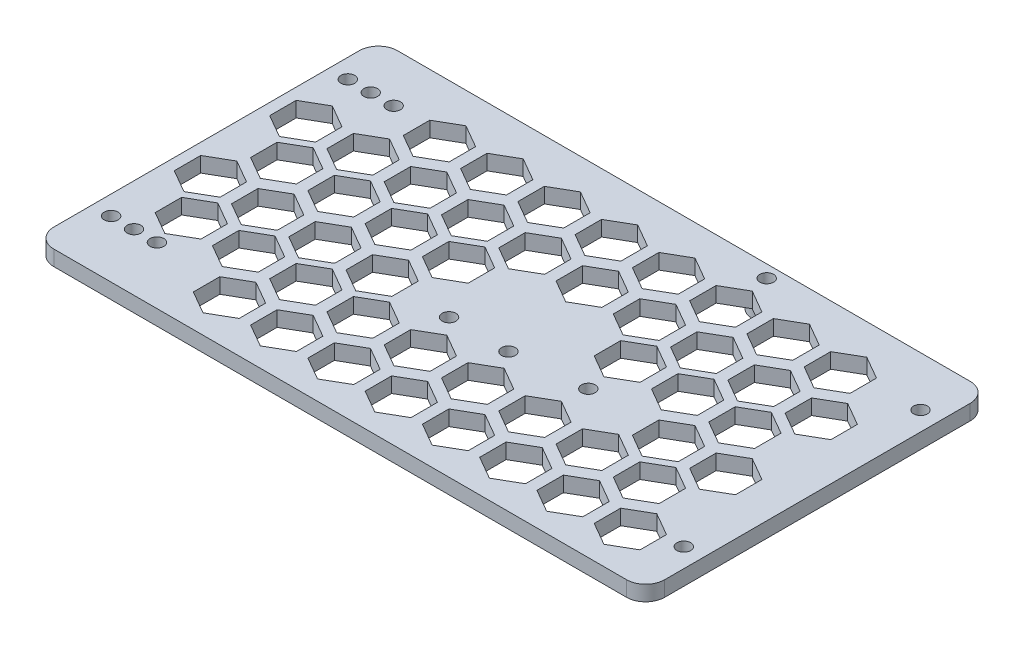
SolidWorks part; units mm, degrees
material "PLA 100% Infill"
ref_plane "Front Plane" through (0, 0, 0) normal (0, 0, 1) x (1, 0, 0)
ref_plane "Top Plane" through (0, 0, 0) normal (0, 1, 0) x (1, 0, 0)
ref_plane "Right Plane" through (0, 0, 0) normal (1, 0, 0) x (0, 0, -1)
sketch "Sketch1" plane through (0, 0, 0) normal (0, 1, 0) x (1, 0, 0)
  line L0 (-160, -45) -> (0, -45) construction
  line L1 (0, 0) -> (-160, 0)
  line L2 (0, 0) -> (0, -90)
  line L3 (0, -90) -> (-160, -90)
  line L4 (-160, 0) -> (-160, -90)
  line L5 (-80, 0) -> (-80, -90) construction
  line L6 (-72.22, -53.71) -> (-87.78, -53.71) construction
  line L7 (-69.22, -51.81) -> (-90.78, -51.81)
  line L8 (-69.22, -56.71) -> (-90.78, -56.71)
  line L9 (-69.22, -56.71) -> (-69.22, -38.71)
  line L10 (-69.22, -38.71) -> (-90.78, -38.71)
  line L11 (-90.78, -56.71) -> (-90.78, -38.71)
  line L12 (-69.22, -56.71) -> (-90.78, -38.71) construction
  line L13 (-69.22, -38.71) -> (-90.78, -56.71) construction
  line L14 (-86.748, -51.81) -> (-84.7188, -53.71)
  line L15 (-73.252, -51.81) -> (-75.2812, -53.71)
  circle A0 centre (-155, -75) radius 1.8
  circle A1 centre (-5, -75) radius 1.8
  circle A2 centre (-5, -13) radius 1.8
  circle A3 centre (-155, -13) radius 1.8
  circle A4 centre (-149, -75) radius 1.8
  circle A5 centre (-149, -13) radius 1.8
  circle A6 centre (-143, -75) radius 1.8
  circle A7 centre (-143, -13) radius 1.8
  circle A8 centre (-72.22, -53.71) radius 1.8
  circle A9 centre (-87.78, -53.71) radius 1.8
  arc A12 (-74.6202, -51.81) -> (-72.8292, -56.71) centre (-72.22, -53.71) ccw
  arc A13 (-85.3798, -51.81) -> (-87.1708, -56.71) centre (-87.78, -53.71) cw
  circle A14 centre (-53.31, -51.7) radius 1.8
  circle A15 centre (-55.02, -3.27) radius 1.8
  point P35 (-80, -58.2721)
  point P45 (-60.3341, -6.5631)
  point P48 (-59.8571, 0)
  point P52 (-57.6313, -4.9732)
  dimension "D3" = 3.6
  dimension "D8" = 62
  dimension "D9" = 5
  dimension "D4" = 30
  dimension "D11" = 3.6
  dimension "D14" = 33.29
  dimension "D20" = 0.1
  dimension "D21" = 3.0612
  dimension "D26" = 3.27
  dimension "D1" = 160
  dimension "D2" = 90
  dimension "D5" = 5
  dimension "D10" = 3
  dimension "D12" = 15.56
  dimension "D13" = 15.56
  dimension "D15" = 3
  dimension "D16" = 3
  dimension "D17" = 3
  dimension "D18" = 18
  dimension "D19" = 3
  dimension "D22" = 4.032
  dimension "D23" = 1.71
  dimension "D24" = 48.43
  dimension "D25" = 55.02
  dimension "D6" = 2
  dimension "D7" = 2
extrude "Boss-Extrude1" add sketch "Sketch1" along normal blind 4 contours L1 L4 L3 L2 A7 A6 A5 A4 A3 A2 A1 A0 L8 L11 L10 L9 | L8 L9 L10 L11 L7 A8 | L7 L8 | L11 L7 L9 L10 | L7 A12 L15 | L15 A12 L8 L9 L7 A8 | A13 L7 L14 | A13 L14 L7 L11 L8 A9 region at (-1.8358, 0, 45) region at (-69.2979, 0, 54.26) region at (-80, 0, 45.26) region at (-74.479, 0, 52.4875) region at (-80, 0, 54.3578) region at (-85.521, 0, 52.4875) region at (-88.9754, 0, 56.6321)
fillet "Fillet1" radius 5 4 edges at (-160, 2, 0) (0, 2, 0) (0, 2, 90) (-160, 2, 90)
extrude "Cut-Extrude1" cut sketch "Sketch1<3>" along normal blind 3 contours L7 A13 L8 A12 | L11 L7 L9 L10 | A13 L7 L14 | L7 A12 L15 region at (-80, 0, 45.26) region at (-74.479, 0, 52.4875) region at (-80, 0, 54.3578) region at (-85.521, 0, 52.4875)
sketch "Sketch1<3>" plane through (0, 0, 0) normal (0, 1, 0) x (1, 0, 0) same geometry as "Sketch1"
sketch "Sketch2" plane through (0, 0, 0) normal (0, -1, 0) x (1, 0, 0)
  line L0 (-5, 0) -> (-155, 0) construction
  line L1 (-52.7163, 0) -> (-57.3237, 0)
  circle A0 centre (-53.31, 51.7) radius 4
  arc A1 (-52.7163, 0) -> (-57.3237, 0) centre (-55.02, 3.27) ccw
  circle A2 centre (-55.02, 3.27) radius 1.8 construction
  circle A3 centre (-53.31, 51.7) radius 1.8 construction
  circle A4 centre (-55.02, 3.27) radius 1.8
  circle A5 centre (-53.31, 51.7) radius 1.8
  dimension "D1" = 8
extrude "Boss-Extrude2" add sketch "Sketch2" along normal blind 3
sketch "Sketch3" plane through (0, 0, 0) normal (0, -1, 0) x (1, 0, 0)
  line L0 (-57.3237, 0) -> (-155, 0) construction
  line L5 (-114.9991, 24.5364) -> (-115.0009, 31.4646)
  line L6 (-123, 11.5359) -> (-123, 18.4641)
  line L7 (-160, 5) -> (-160, 85) construction
  line L164 (-123, 18.4641) -> (-129, 21.9282)
  line L165 (-129, 21.9282) -> (-135, 18.4641)
  line L166 (-135, 18.4641) -> (-135, 11.5359)
  line L167 (-135, 11.5359) -> (-129, 8.0718)
  line L168 (-129, 8.0718) -> (-123, 11.5359)
  line L169 (-115.0009, 31.4646) -> (-121.0009, 34.9287)
  line L170 (-121.0009, 34.9287) -> (-127, 31.463)
  line L171 (-127, 31.463) -> (-127, 24.5348)
  line L172 (-127, 24.5348) -> (-120.9991, 21.0723)
  line L173 (-120.9991, 21.0723) -> (-114.9991, 24.5364)
  line L174 (-108, 11.5359) -> (-108, 18.4641)
  line L175 (-108, 18.4641) -> (-114, 21.9282)
  line L176 (-114, 21.9282) -> (-120, 18.4641)
  line L177 (-120, 18.4641) -> (-120, 11.5359)
  line L178 (-120, 11.5359) -> (-114, 8.0718)
  line L179 (-114, 8.0718) -> (-108, 11.5359)
  line L180 (-99.9991, 24.5364) -> (-100.0009, 31.4646)
  line L181 (-100.0009, 31.4646) -> (-106.0009, 34.9287)
  line L182 (-106.0009, 34.9287) -> (-112, 31.463)
  line L183 (-112, 31.463) -> (-112, 24.5348)
  line L184 (-112, 24.5348) -> (-105.9991, 21.0723)
  line L185 (-105.9991, 21.0723) -> (-99.9991, 24.5364)
  line L186 (-93, 11.5359) -> (-93, 18.4641)
  line L187 (-93, 18.4641) -> (-99, 21.9282)
  line L188 (-99, 21.9282) -> (-105, 18.4641)
  line L189 (-105, 18.4641) -> (-105, 11.5359)
  line L190 (-105, 11.5359) -> (-99, 8.0718)
  line L191 (-99, 8.0718) -> (-93, 11.5359)
  line L192 (-84.9991, 24.5364) -> (-85.0009, 31.4646)
  line L193 (-85.0009, 31.4646) -> (-91.0009, 34.9287)
  line L194 (-91.0009, 34.9287) -> (-97, 31.463)
  line L195 (-97, 31.463) -> (-97, 24.5348)
  line L196 (-97, 24.5348) -> (-90.9991, 21.0723)
  line L197 (-90.9991, 21.0723) -> (-84.9991, 24.5364)
  line L198 (-78, 11.5359) -> (-78, 18.4641)
  line L199 (-78, 18.4641) -> (-84, 21.9282)
  line L200 (-84, 21.9282) -> (-90, 18.4641)
  line L201 (-90, 18.4641) -> (-90, 11.5359)
  line L202 (-90, 11.5359) -> (-84, 8.0718)
  line L203 (-84, 8.0718) -> (-78, 11.5359)
  line L204 (-69.9991, 24.5364) -> (-70.0009, 31.4646)
  line L205 (-70.0009, 31.4646) -> (-76.0009, 34.9287)
  line L206 (-76.0009, 34.9287) -> (-82, 31.463)
  line L207 (-82, 31.463) -> (-82, 24.5348)
  line L208 (-82, 24.5348) -> (-75.9991, 21.0723)
  line L209 (-75.9991, 21.0723) -> (-69.9991, 24.5364)
  line L210 (-63, 11.5359) -> (-63, 18.4641)
  line L211 (-63, 18.4641) -> (-69, 21.9282)
  line L212 (-69, 21.9282) -> (-75, 18.4641)
  line L213 (-75, 18.4641) -> (-75, 11.5359)
  line L214 (-75, 11.5359) -> (-69, 8.0718)
  line L215 (-69, 8.0718) -> (-63, 11.5359)
  line L216 (-54.9991, 24.5364) -> (-55.0009, 31.4646)
  line L217 (-55.0009, 31.4646) -> (-61.0009, 34.9287)
  line L218 (-61.0009, 34.9287) -> (-67, 31.463)
  line L219 (-67, 31.463) -> (-67, 24.5348)
  line L220 (-67, 24.5348) -> (-60.9991, 21.0723)
  line L221 (-60.9991, 21.0723) -> (-54.9991, 24.5364)
  line L222 (-48, 11.5359) -> (-48, 18.4641)
  line L223 (-48, 18.4641) -> (-54, 21.9282)
  line L224 (-54, 21.9282) -> (-60, 18.4641)
  line L225 (-60, 18.4641) -> (-60, 11.5359)
  line L226 (-60, 11.5359) -> (-54, 8.0718)
  line L227 (-54, 8.0718) -> (-48, 11.5359)
  line L228 (-39.9991, 24.5364) -> (-40.0009, 31.4646)
  line L229 (-40.0009, 31.4646) -> (-46.0009, 34.9287)
  line L230 (-46.0009, 34.9287) -> (-52, 31.463)
  line L231 (-52, 31.463) -> (-52, 24.5348)
  line L232 (-52, 24.5348) -> (-45.9991, 21.0723)
  line L233 (-45.9991, 21.0723) -> (-39.9991, 24.5364)
  line L234 (-33, 11.5359) -> (-33, 18.4641)
  line L235 (-33, 18.4641) -> (-39, 21.9282)
  line L236 (-39, 21.9282) -> (-45, 18.4641)
  line L237 (-45, 18.4641) -> (-45, 11.5359)
  line L238 (-45, 11.5359) -> (-39, 8.0718)
  line L239 (-39, 8.0718) -> (-33, 11.5359)
  line L240 (-24.9991, 24.5364) -> (-25.0009, 31.4646)
  line L241 (-25.0009, 31.4646) -> (-31.0009, 34.9287)
  line L242 (-31.0009, 34.9287) -> (-37, 31.463)
  line L243 (-37, 31.463) -> (-37, 24.5348)
  line L244 (-37, 24.5348) -> (-30.9991, 21.0723)
  line L245 (-30.9991, 21.0723) -> (-24.9991, 24.5364)
  line L246 (-18, 11.5359) -> (-18, 18.4641)
  line L247 (-18, 18.4641) -> (-24, 21.9282)
  line L248 (-24, 21.9282) -> (-30, 18.4641)
  line L249 (-30, 18.4641) -> (-30, 11.5359)
  line L250 (-30, 11.5359) -> (-24, 8.0718)
  line L251 (-24, 8.0718) -> (-18, 11.5359)
  line L252 (-9.9991, 24.5364) -> (-10.0009, 31.4646)
  line L253 (-10.0009, 31.4646) -> (-16.0009, 34.9287)
  line L254 (-16.0009, 34.9287) -> (-22, 31.463)
  line L255 (-22, 31.463) -> (-22, 24.5348)
  line L256 (-22, 24.5348) -> (-15.9991, 21.0723)
  line L257 (-15.9991, 21.0723) -> (-9.9991, 24.5364)
  line L258 (-108, 36.5359) -> (-108, 43.4641)
  line L259 (-108, 43.4641) -> (-114, 46.9282)
  line L260 (-114, 46.9282) -> (-120, 43.4641)
  line L261 (-120, 43.4641) -> (-120, 36.5359)
  line L262 (-120, 36.5359) -> (-114, 33.0718)
  line L263 (-114, 33.0718) -> (-108, 36.5359)
  line L264 (-99.9991, 49.5364) -> (-100.0009, 56.4646)
  line L265 (-100.0009, 56.4646) -> (-106.0009, 59.9287)
  line L266 (-106.0009, 59.9287) -> (-112, 56.463)
  line L267 (-112, 56.463) -> (-112, 49.5348)
  line L268 (-112, 49.5348) -> (-105.9991, 46.0723)
  line L269 (-105.9991, 46.0723) -> (-99.9991, 49.5364)
  line L270 (-93, 36.5359) -> (-93, 43.4641)
  line L271 (-93, 43.4641) -> (-99, 46.9282)
  line L272 (-99, 46.9282) -> (-105, 43.4641)
  line L273 (-105, 43.4641) -> (-105, 36.5359)
  line L274 (-105, 36.5359) -> (-99, 33.0718)
  line L275 (-99, 33.0718) -> (-93, 36.5359)
  line L306 (-48, 36.5359) -> (-48, 43.4641)
  line L307 (-48, 43.4641) -> (-54, 46.9282)
  line L308 (-54, 46.9282) -> (-60, 43.4641)
  line L309 (-60, 43.4641) -> (-60, 36.5359)
  line L310 (-60, 36.5359) -> (-54, 33.0718)
  line L311 (-54, 33.0718) -> (-48, 36.5359)
  line L318 (-33, 36.5359) -> (-33, 43.4641)
  line L319 (-33, 43.4641) -> (-39, 46.9282)
  line L320 (-39, 46.9282) -> (-45, 43.4641)
  line L321 (-45, 43.4641) -> (-45, 36.5359)
  line L322 (-45, 36.5359) -> (-39, 33.0718)
  line L323 (-39, 33.0718) -> (-33, 36.5359)
  line L324 (-24.9991, 49.5364) -> (-25.0009, 56.4646)
  line L325 (-25.0009, 56.4646) -> (-31.0009, 59.9287)
  line L326 (-31.0009, 59.9287) -> (-37, 56.463)
  line L327 (-37, 56.463) -> (-37, 49.5348)
  line L328 (-37, 49.5348) -> (-30.9991, 46.0723)
  line L329 (-30.9991, 46.0723) -> (-24.9991, 49.5364)
  line L330 (-18, 36.5359) -> (-18, 43.4641)
  line L331 (-18, 43.4641) -> (-24, 46.9282)
  line L332 (-24, 46.9282) -> (-30, 43.4641)
  line L333 (-30, 43.4641) -> (-30, 36.5359)
  line L334 (-30, 36.5359) -> (-24, 33.0718)
  line L335 (-24, 33.0718) -> (-18, 36.5359)
  line L336 (-9.9991, 49.5364) -> (-10.0009, 56.4646)
  line L337 (-10.0009, 56.4646) -> (-16.0009, 59.9287)
  line L338 (-16.0009, 59.9287) -> (-22, 56.463)
  line L339 (-22, 56.463) -> (-22, 49.5348)
  line L340 (-22, 49.5348) -> (-15.9991, 46.0723)
  line L341 (-15.9991, 46.0723) -> (-9.9991, 49.5364)
  line L342 (-108, 61.5359) -> (-108, 68.4641)
  line L343 (-108, 68.4641) -> (-114, 71.9282)
  line L344 (-114, 71.9282) -> (-120, 68.4641)
  line L345 (-120, 68.4641) -> (-120, 61.5359)
  line L346 (-120, 61.5359) -> (-114, 58.0718)
  line L347 (-114, 58.0718) -> (-108, 61.5359)
  line L348 (-99.9991, 74.5364) -> (-100.0009, 81.4646)
  line L349 (-100.0009, 81.4646) -> (-106.0009, 84.9287)
  line L350 (-106.0009, 84.9287) -> (-112, 81.463)
  line L351 (-112, 81.463) -> (-112, 74.5348)
  line L352 (-112, 74.5348) -> (-105.9991, 71.0723)
  line L353 (-105.9991, 71.0723) -> (-99.9991, 74.5364)
  line L354 (-93, 61.5359) -> (-93, 68.4641)
  line L355 (-93, 68.4641) -> (-99, 71.9282)
  line L356 (-99, 71.9282) -> (-105, 68.4641)
  line L357 (-105, 68.4641) -> (-105, 61.5359)
  line L358 (-105, 61.5359) -> (-99, 58.0718)
  line L359 (-99, 58.0718) -> (-93, 61.5359)
  line L360 (-84.9991, 74.5364) -> (-85.0009, 81.4646)
  line L361 (-85.0009, 81.4646) -> (-91.0009, 84.9287)
  line L362 (-91.0009, 84.9287) -> (-97, 81.463)
  line L363 (-97, 81.463) -> (-97, 74.5348)
  line L364 (-97, 74.5348) -> (-90.9991, 71.0723)
  line L365 (-90.9991, 71.0723) -> (-84.9991, 74.5364)
  line L366 (-78, 61.5359) -> (-78, 68.4641)
  line L367 (-78, 68.4641) -> (-84, 71.9282)
  line L368 (-84, 71.9282) -> (-90, 68.4641)
  line L369 (-90, 68.4641) -> (-90, 61.5359)
  line L370 (-90, 61.5359) -> (-84, 58.0718)
  line L371 (-84, 58.0718) -> (-78, 61.5359)
  line L372 (-69.9991, 74.5364) -> (-70.0009, 81.4646)
  line L373 (-70.0009, 81.4646) -> (-76.0009, 84.9287)
  line L374 (-76.0009, 84.9287) -> (-82, 81.463)
  line L375 (-82, 81.463) -> (-82, 74.5348)
  line L376 (-82, 74.5348) -> (-75.9991, 71.0723)
  line L377 (-75.9991, 71.0723) -> (-69.9991, 74.5364)
  line L378 (-63, 61.5359) -> (-63, 68.4641)
  line L379 (-63, 68.4641) -> (-69, 71.9282)
  line L380 (-69, 71.9282) -> (-75, 68.4641)
  line L381 (-75, 68.4641) -> (-75, 61.5359)
  line L382 (-75, 61.5359) -> (-69, 58.0718)
  line L383 (-69, 58.0718) -> (-63, 61.5359)
  line L384 (-54.9991, 74.5364) -> (-55.0009, 81.4646)
  line L385 (-55.0009, 81.4646) -> (-61.0009, 84.9287)
  line L386 (-61.0009, 84.9287) -> (-67, 81.463)
  line L387 (-67, 81.463) -> (-67, 74.5348)
  line L388 (-67, 74.5348) -> (-60.9991, 71.0723)
  line L389 (-60.9991, 71.0723) -> (-54.9991, 74.5364)
  line L390 (-48, 61.5359) -> (-48, 68.4641)
  line L391 (-48, 68.4641) -> (-54, 71.9282)
  line L392 (-54, 71.9282) -> (-60, 68.4641)
  line L393 (-60, 68.4641) -> (-60, 61.5359)
  line L394 (-60, 61.5359) -> (-54, 58.0718)
  line L395 (-54, 58.0718) -> (-48, 61.5359)
  line L396 (-39.9991, 74.5364) -> (-40.0009, 81.4646)
  line L397 (-40.0009, 81.4646) -> (-46.0009, 84.9287)
  line L398 (-46.0009, 84.9287) -> (-52, 81.463)
  line L399 (-52, 81.463) -> (-52, 74.5348)
  line L400 (-52, 74.5348) -> (-45.9991, 71.0723)
  line L401 (-45.9991, 71.0723) -> (-39.9991, 74.5364)
  line L402 (-33, 61.5359) -> (-33, 68.4641)
  line L403 (-33, 68.4641) -> (-39, 71.9282)
  line L404 (-39, 71.9282) -> (-45, 68.4641)
  line L405 (-45, 68.4641) -> (-45, 61.5359)
  line L406 (-45, 61.5359) -> (-39, 58.0718)
  line L407 (-39, 58.0718) -> (-33, 61.5359)
  line L408 (-24.9991, 74.5364) -> (-25.0009, 81.4646)
  line L409 (-25.0009, 81.4646) -> (-31.0009, 84.9287)
  line L410 (-31.0009, 84.9287) -> (-37, 81.463)
  line L411 (-37, 81.463) -> (-37, 74.5348)
  line L412 (-37, 74.5348) -> (-30.9991, 71.0723)
  line L413 (-30.9991, 71.0723) -> (-24.9991, 74.5364)
  line L414 (-18, 61.5359) -> (-18, 68.4641)
  line L415 (-18, 68.4641) -> (-24, 71.9282)
  line L416 (-24, 71.9282) -> (-30, 68.4641)
  line L417 (-30, 68.4641) -> (-30, 61.5359)
  line L418 (-30, 61.5359) -> (-24, 58.0718)
  line L419 (-24, 58.0718) -> (-18, 61.5359)
  line L420 (-9.9991, 74.5364) -> (-10.0009, 81.4646)
  line L421 (-10.0009, 81.4646) -> (-16.0009, 84.9287)
  line L422 (-16.0009, 84.9287) -> (-22, 81.463)
  line L423 (-22, 81.463) -> (-22, 74.5348)
  line L424 (-22, 74.5348) -> (-15.9991, 71.0723)
  line L425 (-15.9991, 71.0723) -> (-9.9991, 74.5364)
  line L426 (-123, 36.5359) -> (-123, 43.4641)
  line L427 (-123, 43.4641) -> (-129, 46.9282)
  line L428 (-129, 46.9282) -> (-135, 43.4641)
  line L429 (-135, 43.4641) -> (-135, 36.5359)
  line L430 (-135, 36.5359) -> (-129, 33.0718)
  line L431 (-129, 33.0718) -> (-123, 36.5359)
  line L432 (-114.9991, 49.5364) -> (-115.0009, 56.4646)
  line L433 (-115.0009, 56.4646) -> (-121.0009, 59.9287)
  line L434 (-121.0009, 59.9287) -> (-127, 56.463)
  line L435 (-127, 56.463) -> (-127, 49.5348)
  line L436 (-127, 49.5348) -> (-120.9991, 46.0723)
  line L437 (-120.9991, 46.0723) -> (-114.9991, 49.5364)
  line L438 (-123, 61.5359) -> (-123, 68.4641)
  line L439 (-123, 68.4641) -> (-129, 71.9282)
  line L440 (-129, 71.9282) -> (-135, 68.4641)
  line L441 (-135, 68.4641) -> (-135, 61.5359)
  line L442 (-135, 61.5359) -> (-129, 58.0718)
  line L443 (-129, 58.0718) -> (-123, 61.5359)
  line L444 (-114.9991, 74.5364) -> (-115.0009, 81.4646)
  line L445 (-115.0009, 81.4646) -> (-121.0009, 84.9287)
  line L446 (-121.0009, 84.9287) -> (-127, 81.463)
  line L447 (-127, 81.463) -> (-127, 74.5348)
  line L448 (-127, 74.5348) -> (-120.9991, 71.0723)
  line L449 (-120.9991, 71.0723) -> (-114.9991, 74.5364)
  line L456 (-129.9991, 24.5364) -> (-130.0009, 31.4646)
  line L457 (-130.0009, 31.4646) -> (-136.0009, 34.9287)
  line L458 (-136.0009, 34.9287) -> (-142, 31.463)
  line L459 (-142, 31.463) -> (-142, 24.5348)
  line L460 (-142, 24.5348) -> (-135.9991, 21.0723)
  line L461 (-135.9991, 21.0723) -> (-129.9991, 24.5364)
  line L462 (-138, 36.5359) -> (-138, 43.4641)
  line L463 (-138, 43.4641) -> (-144, 46.9282)
  line L464 (-144, 46.9282) -> (-150, 43.4641)
  line L465 (-150, 43.4641) -> (-150, 36.5359)
  line L466 (-150, 36.5359) -> (-144, 33.0718)
  line L467 (-144, 33.0718) -> (-138, 36.5359)
  line L468 (-129.9991, 49.5364) -> (-130.0009, 56.4646)
  line L469 (-130.0009, 56.4646) -> (-136.0009, 59.9287)
  line L470 (-136.0009, 59.9287) -> (-142, 56.463)
  line L471 (-142, 56.463) -> (-142, 49.5348)
  line L472 (-142, 49.5348) -> (-135.9991, 46.0723)
  line L473 (-135.9991, 46.0723) -> (-129.9991, 49.5364)
  line L474 (-138, 61.5359) -> (-138, 68.4641)
  line L475 (-138, 68.4641) -> (-144, 71.9282)
  line L476 (-144, 71.9282) -> (-150, 68.4641)
  line L477 (-150, 68.4641) -> (-150, 61.5359)
  line L478 (-150, 61.5359) -> (-144, 58.0718)
  line L479 (-144, 58.0718) -> (-138, 61.5359)
  line L492 (-144.9991, 24.5364) -> (-145.0009, 31.4646)
  line L493 (-145.0009, 31.4646) -> (-151.0009, 34.9287)
  line L494 (-151.0009, 34.9287) -> (-157, 31.463)
  line L495 (-157, 31.463) -> (-157, 24.5348)
  line L496 (-157, 24.5348) -> (-150.9991, 21.0723)
  line L497 (-150.9991, 21.0723) -> (-144.9991, 24.5364)
  line L504 (-144.9991, 49.5364) -> (-145.0009, 56.4646)
  line L505 (-145.0009, 56.4646) -> (-151.0009, 59.9287)
  line L506 (-151.0009, 59.9287) -> (-157, 56.463)
  line L507 (-157, 56.463) -> (-157, 49.5348)
  line L508 (-157, 49.5348) -> (-150.9991, 46.0723)
  line L509 (-150.9991, 46.0723) -> (-144.9991, 49.5364)
  line L522 (-153, 18.4641) -> (-159, 21.9282) [skipped]
  line L523 (-165, 11.5359) -> (-159, 8.0718) [skipped]
  line L524 (-159, 8.0718) -> (-153, 11.5359) [skipped]
  line L525 (-150, 18.4641) -> (-150, 11.5359) [skipped]
  line L526 (-150, 11.5359) -> (-144, 8.0718) [skipped]
  line L527 (-153, 11.5359) -> (-153, 18.4641) [skipped]
  line L528 (-144, 8.0718) -> (-138, 11.5359) [skipped]
  line L529 (-138, 11.5359) -> (-138, 18.4641) [skipped]
  line L530 (-138, 18.4641) -> (-144, 21.9282) [skipped]
  line L531 (-144, 21.9282) -> (-150, 18.4641) [skipped]
  line L532 (-159, 21.9282) -> (-165, 18.4641) [skipped]
  line L533 (-165, 18.4641) -> (-165, 11.5359) [skipped]
  line L534 (-159, 33.0718) -> (-153, 36.5359) [skipped]
  line L535 (-153, 36.5359) -> (-153, 43.4641) [skipped]
  line L536 (-153, 43.4641) -> (-159, 46.9282) [skipped]
  line L537 (-165, 36.5359) -> (-159, 33.0718) [skipped]
  line L538 (-165, 43.4641) -> (-165, 36.5359) [skipped]
  line L539 (-159, 46.9282) -> (-165, 43.4641) [skipped]
  line L540 (-157, 74.5348) -> (-150.9991, 71.0723) [skipped]
  line L541 (-144.9991, 74.5364) -> (-145.0009, 81.4646) [skipped]
  line L542 (-142, 81.463) -> (-142, 74.5348) [skipped]
  line L543 (-142, 74.5348) -> (-135.9991, 71.0723) [skipped]
  line L544 (-150.9991, 71.0723) -> (-144.9991, 74.5364) [skipped]
  line L545 (-135.9991, 71.0723) -> (-129.9991, 74.5364) [skipped]
  line L546 (-129.9991, 74.5364) -> (-130.0009, 81.4646) [skipped]
  line L547 (-136.0009, 84.9287) -> (-142, 81.463) [skipped]
  line L548 (-130.0009, 81.4646) -> (-136.0009, 84.9287) [skipped]
  line L549 (-145.0009, 81.4646) -> (-151.0009, 84.9287) [skipped]
  line L550 (-157, 81.463) -> (-157, 74.5348) [skipped]
  line L551 (-151.0009, 84.9287) -> (-157, 81.463) [skipped]
  line L552 (-153, 68.4641) -> (-159, 71.9282) [skipped]
  line L553 (-153, 61.5359) -> (-153, 68.4641) [skipped]
  line L554 (-159, 58.0718) -> (-153, 61.5359) [skipped]
  line L555 (-165, 61.5359) -> (-159, 58.0718) [skipped]
  line L556 (-159, 71.9282) -> (-165, 68.4641) [skipped]
  line L557 (-165, 68.4641) -> (-165, 61.5359) [skipped]
  line L558 (-97, 56.463) -> (-97, 49.5348) [skipped]
  line L559 (-97, 49.5348) -> (-90.9991, 46.0723) [skipped]
  line L560 (-90.9991, 46.0723) -> (-84.9991, 49.5364) [skipped]
  line L561 (-82, 49.5348) -> (-75.9991, 46.0723) [skipped]
  line L562 (-75.9991, 46.0723) -> (-69.9991, 49.5364) [skipped]
  line L563 (-67, 49.5348) -> (-60.9991, 46.0723) [skipped]
  line L564 (-60.9991, 46.0723) -> (-54.9991, 49.5364) [skipped]
  line L565 (-40.0009, 56.4646) -> (-46.0009, 59.9287) [skipped]
  line L566 (-39.9991, 49.5364) -> (-40.0009, 56.4646) [skipped]
  line L567 (-45.9991, 46.0723) -> (-39.9991, 49.5364) [skipped]
  line L568 (-52, 49.5348) -> (-45.9991, 46.0723) [skipped]
  line L569 (-67, 56.463) -> (-67, 49.5348) [skipped]
  line L570 (-69.9991, 49.5364) -> (-70.0009, 56.4646) [skipped]
  line L571 (-82, 56.463) -> (-82, 49.5348) [skipped]
  line L572 (-84.9991, 49.5364) -> (-85.0009, 56.4646) [skipped]
  line L573 (-91.0009, 59.9287) -> (-97, 56.463) [skipped]
  line L574 (-85.0009, 56.4646) -> (-91.0009, 59.9287) [skipped]
  line L575 (-76.0009, 59.9287) -> (-82, 56.463) [skipped]
  line L576 (-70.0009, 56.4646) -> (-76.0009, 59.9287) [skipped]
  line L577 (-61.0009, 59.9287) -> (-67, 56.463) [skipped]
  line L578 (-55.0009, 56.4646) -> (-61.0009, 59.9287) [skipped]
  line L579 (-46.0009, 59.9287) -> (-52, 56.463) [skipped]
  line L580 (-52, 56.463) -> (-52, 49.5348) [skipped]
  line L581 (-54.9991, 49.5364) -> (-55.0009, 56.4646) [skipped]
  line L582 (-78, 43.4641) -> (-84, 46.9282) [skipped]
  line L583 (-84, 46.9282) -> (-90, 43.4641) [skipped]
  line L584 (-90, 43.4641) -> (-90, 36.5359) [skipped]
  line L585 (-90, 36.5359) -> (-84, 33.0718) [skipped]
  line L586 (-84, 33.0718) -> (-78, 36.5359) [skipped]
  line L587 (-78, 36.5359) -> (-78, 43.4641) [skipped]
  line L588 (-75, 43.4641) -> (-75, 36.5359) [skipped]
  line L589 (-69, 46.9282) -> (-75, 43.4641) [skipped]
  line L590 (-63, 43.4641) -> (-69, 46.9282) [skipped]
  line L591 (-63, 36.5359) -> (-63, 43.4641) [skipped]
  line L592 (-69, 33.0718) -> (-63, 36.5359) [skipped]
  line L593 (-75, 36.5359) -> (-69, 33.0718) [skipped]
  circle A0 centre (-129, 15) radius 6 construction
  circle A1 centre (-121, 28) radius 6 construction
  dimension "D1" = 12
  dimension "D2" = 8
  dimension "D3" = 13
  dimension "D4" = 15
  dimension "D5" = 31
  dimension "D6" = 8
  dimension "D7" = 3
extrude "Cut-Extrude2" cut sketch "Sketch3" against normal through all
